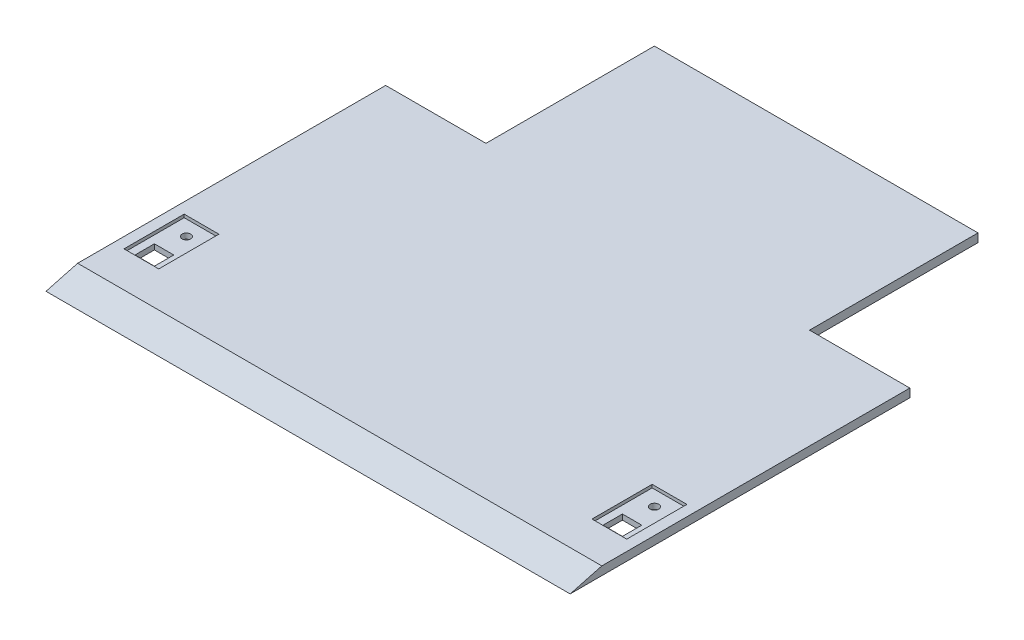
SolidWorks part; units mm, degrees
ref_plane "Alzado" through (0, 0, 0) normal (0, 0, 1) x (1, 0, 0)
ref_plane "Planta" through (0, 0, 0) normal (0, 1, 0) x (1, 0, 0)
ref_plane "Vista lateral" through (0, 0, 0) normal (1, 0, 0) x (0, 0, -1)
sketch "Croquis1" plane through (0, 0, 0) normal (1, 0, 0) x (0, 0, -1)
  line L0 (0, 0) -> (190, 0)
  line L1 (190, 0) -> (190, 3.17)
  line L2 (190, 3.17) -> (11.8306, 3.17)
  line L3 (0, 0) -> (11.8306, 3.17)
  dimension "D1" = 190
  dimension "D2" = 3.17
  dimension "D3" = 165
extrude "Saliente-Extruir1" add sketch "Croquis1" along normal blind 196
sketch "Croquis2" plane through (0, 0, 0) normal (0, -1, 0) x (-1, 0, 0)
  line L0 (0, 190) -> (0, 11.8306) construction
  line L1 (0, 127.0101) -> (-37.5, 127.0101)
  line L2 (0, 127.0101) -> (0, 190)
  line L3 (0, 190) -> (-37.5, 190)
  line L4 (-37.5, 127.0101) -> (-37.5, 190)
  line L5 (0, 127.0101) -> (-37.5, 190) construction
  line L6 (0, 190) -> (-37.5, 127.0101) construction
  line L7 (-196, 127.0101) -> (0, 127.0101) construction
  line L8 (-196, 190) -> (0, 190) construction
  line L9 (-37.5, 131.5) -> (-37.5, 190) construction
  point P4 (-18.75, 158.5051)
extrude "Cortar-Extruir1" cut sketch "Croquis2" against normal up to next
ref_plane "Plano1" through (98, 0, 0) normal (-1, 0, 0) x (0, 0, 1)
mirror "Simetría1" about plane through (98, 0, 0) normal (-1, 0, 0) of "Cortar-Extruir1"
sketch "Croquis3" plane through (0, 3.17, 0) normal (0, 1, 0) x (1, 0, 0)
  line L0 (196, 0) -> (0, 0) construction
  line L1 (4, 47.66) -> (17, 47.66)
  line L2 (4, 47.66) -> (4, 25.16)
  line L3 (4, 25.16) -> (17, 25.16)
  line L4 (17, 47.66) -> (17, 25.16)
  line L5 (4, 47.66) -> (17, 25.16) construction
  line L6 (4, 25.16) -> (17, 47.66) construction
  line L7 (0, 127.0101) -> (0, 11.8306) construction
  point P4 (10.5, 36.41)
  dimension "D1" = 25.16
  dimension "D2" = 22.5
  dimension "D3" = 13
  dimension "D4" = 4
extrude "Cortar-Extruir2" cut sketch "Croquis3" against normal blind 1.17
sketch "Croquis4" plane through (0, 2, 0) normal (0, 1, 0) x (1, 0, 0)
  line L0 (10.5, 25.16) -> (10.5, 26.41) construction
  line L1 (4, 25.16) -> (17, 25.16) construction
  line L2 (4, 26.41) -> (17, 26.41) construction
  line L3 (4, 47.66) -> (4, 25.16) construction
  line L4 (17, 25.16) -> (17, 47.66) construction
  line L5 (10.5, 26.41) -> (10.5, 33.66) construction
  line L6 (10.5, 30.035) -> (6.875, 30.035) construction
  line L7 (10.5, 30.035) -> (14.125, 30.035) construction
  line L8 (6.875, 30.035) -> (6.875, 26.41) construction
  line L9 (14.125, 30.035) -> (14.125, 33.66) construction
  dimension "D1" = 1.25
  dimension "D2" = 7.25
  dimension "D3" = 3.625
  dimension "D4" = 3.625
sketch "Croquis5" plane through (0, 2, 0) normal (0, 1, 0) x (1, 0, 0)
  line L1 (6.875, 26.41) -> (14.125, 26.41)
  line L2 (6.875, 26.41) -> (6.875, 33.66)
  line L3 (6.875, 33.66) -> (14.125, 33.66)
  line L4 (14.125, 26.41) -> (14.125, 33.66)
  line L5 (6.875, 26.41) -> (14.125, 33.66) construction
  line L6 (6.875, 33.66) -> (14.125, 26.41) construction
  point P4 (10.5, 30.035)
extrude "Cortar-Extruir3" cut sketch "Croquis5" against normal up to next
sketch "Croquis6" plane through (0, 2, 0) normal (0, 1, 0) x (1, 0, 0)
  line L0 (10.5, 47.66) -> (10.5, 46.41) construction
  line L1 (17, 47.66) -> (4, 47.66) construction
  line L2 (10.5, 46.41) -> (17, 46.41) construction
  line L3 (17, 25.16) -> (17, 47.66) construction
  line L4 (17, 46.41) -> (4, 46.41) construction
  line L5 (4, 47.66) -> (4, 25.16) construction
  circle A0 centre (10.5, 42.01) radius 1.6
  dimension "D2" = 3.2
  dimension "D1" = 1.25
  dimension "D3" = 4.4
extrude "Cortar-Extruir4" cut sketch "Croquis6" against normal up to next
mirror "Simetría2" about plane through (98, 0, 0) normal (-1, 0, 0) of "Cortar-Extruir2", "Cortar-Extruir4", "Cortar-Extruir3"
